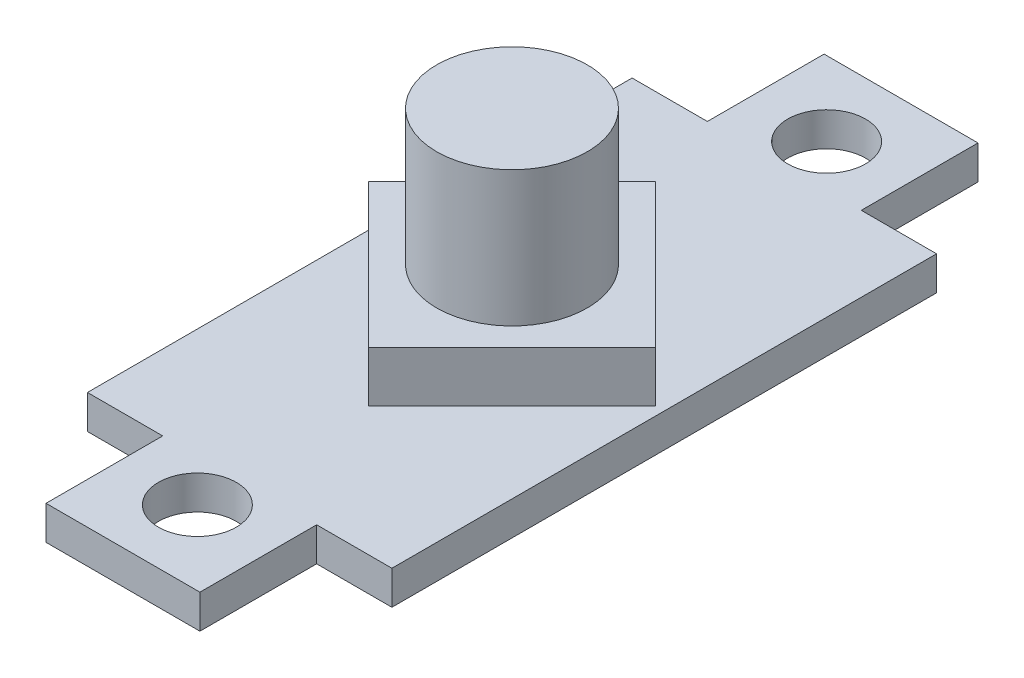
SolidWorks part; units mm, degrees
ref_plane "Front Plane" through (0, 0, 0) normal (0, 0, 1) x (1, 0, 0)
ref_plane "Top Plane" through (0, 0, 0) normal (0, 1, 0) x (1, 0, 0)
ref_plane "Right Plane" through (0, 0, 0) normal (1, 0, 0) x (0, 0, -1)
sketch "Sketch1" plane through (0, 0, 0) normal (0, 1, 0) x (1, 0, 0)
  line L0 (0, 11.5) -> (0, -11.5) construction
  line L1 (-4.5, 11.5) -> (4.5, 11.5)
  line L2 (-4.5, 11.5) -> (-4.5, -11.5)
  line L3 (-4.5, -11.5) -> (4.5, -11.5)
  line L4 (4.5, 11.5) -> (4.5, -11.5)
  line L5 (-4.5, 11.5) -> (4.5, -11.5) construction
  line L6 (-4.5, -11.5) -> (4.5, 11.5) construction
  line L7 (-2.275, 11.5) -> (2.275, 11.5)
  line L8 (-2.275, 11.5) -> (-2.275, -11.5)
  line L9 (-2.275, -11.5) -> (2.275, -11.5)
  line L10 (2.275, 11.5) -> (2.275, -11.5)
  line L11 (-2.275, 11.5) -> (2.275, -11.5) construction
  line L12 (-2.275, -11.5) -> (2.275, 11.5) construction
  line L13 (4.5, 8.05) -> (-4.5, 8.05)
  line L14 (4.5, 8.05) -> (4.5, -8.05)
  line L15 (4.5, -8.05) -> (-4.5, -8.05)
  line L16 (-4.5, 8.05) -> (-4.5, -8.05)
  line L17 (4.5, 8.05) -> (-4.5, -8.05) construction
  line L18 (4.5, -8.05) -> (-4.5, 8.05) construction
  line L19 (-4.5, 0) -> (4.5, 0) construction
  circle A0 centre (0, 9.3) radius 1.15
  circle A1 centre (0, -9.3) radius 1.15
  point P0 (0, 0)
  point P6 (0, 0)
  point P11 (0, 0)
  dimension "D6" = 2.3
  dimension "D1" = 9
  dimension "D2" = 23
  dimension "D3" = 4.55
  dimension "D4" = 16.1
  dimension "D5" = 18.6
extrude "Boss-Extrude1" add sketch "Sketch1" along normal blind 1 contours L15 L8 L13 L2 | L13 L10 L1 L8 A0 | L15 L10 L13 L8 | L15 L4 L13 L10 | L10 L15 L8 L3 A1 region at (0, 0, -11.4429) region at (-3.3875, 0, 0) region at (0, 0, 0) region at (3.3875, 0, 0) region at (0, 0, 8.1071)
sketch "Sketch2" plane through (0, 1, 0) normal (0, 1, 0) x (1, 0, 0)
  line L0 (0, 11.5) -> (0, -11.5) construction
  line L1 (0, -4.2426) -> (4.2426, 0)
  line L2 (4.2426, 0) -> (0, 4.2426)
  line L3 (0, 4.2426) -> (-4.2426, 0)
  line L4 (-4.2426, 0) -> (0, -4.2426)
  line L5 (-2.275, 11.5) -> (2.275, 11.5) construction
  line L6 (-2.275, -11.5) -> (2.275, -11.5) construction
  circle A0 centre (0, 0) radius 3 construction
  dimension "D1" = 6
extrude "Boss-Extrude2" add sketch "Sketch2" along normal blind 1.5
sketch "Sketch3" plane through (0, 2.5, 0) normal (0, 1, 0) x (1, 0, 0)
  circle A0 centre (0, 0) radius 2.2266
extrude "Boss-Extrude3" add sketch "Sketch3" along normal blind 4
